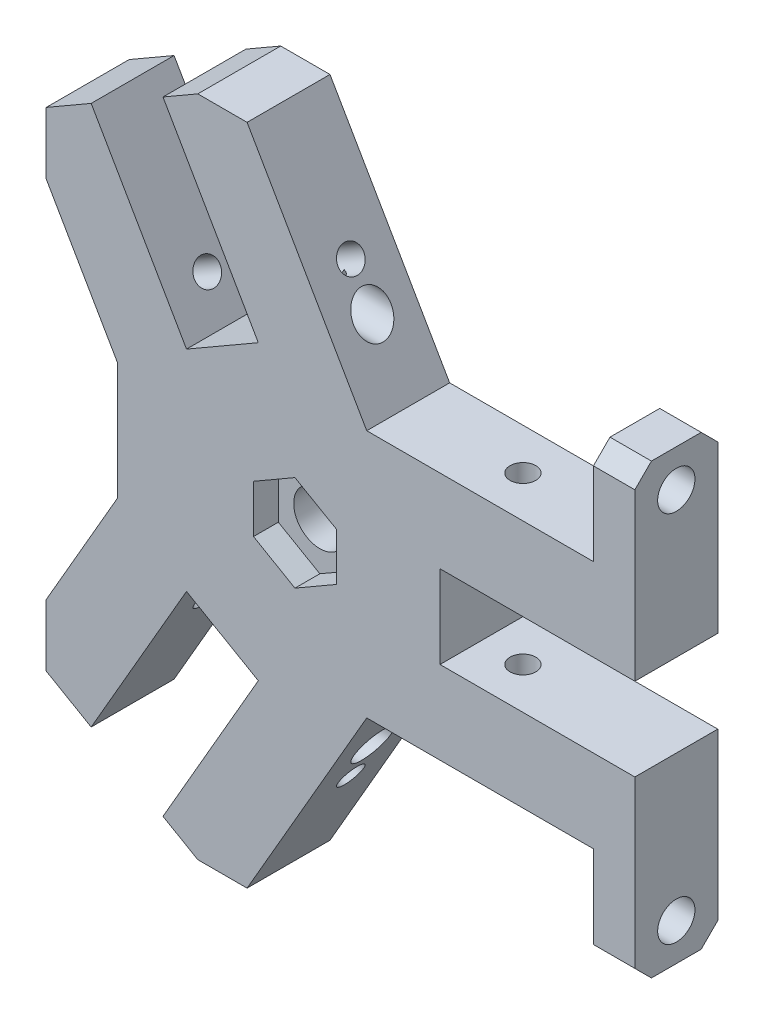
SolidWorks part; units mm, degrees
ref_plane "Front" through (0, 0, 0) normal (0, 0, 1) x (1, 0, 0)
ref_plane "Top" through (0, 0, 0) normal (0, 1, 0) x (1, 0, 0)
ref_plane "Right" through (0, 0, 0) normal (1, 0, 0) x (0, 0, -1)
sketch "Sketch1" plane through (0, 0, 0) normal (0, 0, 1) x (1, 0, 0)
  line L1 (0, 0) -> (71, 0)
  line L2 (0, 0) -> (0, 80)
  line L3 (0, 80) -> (71, 80)
  line L4 (71, 0) -> (71, 80)
  dimension "D1" = 80
  dimension "D2" = 71
extrude "Boss-Extrude1" add sketch "Sketch1" along normal blind 10
sketch "Sketch2" plane through (0, 0, 10) normal (0, 0, 1) x (1, 0, 0)
  line L1 (0, 80) -> (0, 0) construction
  line L2 (18.75, 59.4856) -> (18.75, 20.5144) construction
  line L3 (18.75, 20.5144) -> (52.5, 40) construction
  line L4 (52.5, 40) -> (18.75, 59.4856) construction
  circle A0 centre (30, 40) radius 22.5 construction
  point P3 (0, 40)
  dimension "D1" = 22.5
  dimension "D3" = 30
ref_axis "Axis1" through (30, 40, 10) along (0, 0, -1)
sketch "Sketch3" plane through (0, 0, 10) normal (0, 0, 1) x (1, 0, 0)
  line L0 (25.5801, 57.6554) -> (16.9199, 52.6554)
  line L1 (25.5801, 57.6554) -> (20.5801, 66.3157)
  line L2 (16.9199, 52.6554) -> (11.9199, 61.3157)
  line L3 (20.5801, 66.3157) -> (11.9199, 61.3157)
  line L4 (25.5801, 57.6554) -> (11.9199, 61.3157) construction
  line L5 (16.9199, 52.6554) -> (20.5801, 66.3157) construction
  line L6 (11.9199, 18.6843) -> (20.5801, 13.6843)
  line L7 (11.9199, 18.6843) -> (16.9199, 27.3446)
  line L8 (20.5801, 13.6843) -> (25.5801, 22.3446)
  line L9 (16.9199, 27.3446) -> (25.5801, 22.3446)
  line L10 (11.9199, 18.6843) -> (25.5801, 22.3446) construction
  line L11 (20.5801, 13.6843) -> (16.9199, 27.3446) construction
  line L13 (47.5, 45) -> (57.5, 45)
  line L14 (47.5, 45) -> (47.5, 35)
  line L15 (47.5, 35) -> (57.5, 35)
  line L16 (57.5, 45) -> (57.5, 35)
  line L17 (47.5, 45) -> (57.5, 35) construction
  line L18 (47.5, 35) -> (57.5, 45) construction
  point P0 (52.5, 40)
  point P1 (18.75, 59.4856)
  point P2 (18.75, 20.5144)
  dimension "D1" = 60
  dimension "D2" = 60
  dimension "D3" = 10
  dimension "D4" = 10
  dimension "D5" = 10
  dimension "D6" = 10
  dimension "D7" = 10
  dimension "D8" = 10
extrude "Cut-Extrude1" cut sketch "Sketch3" against normal blind 10
sketch "Sketch4" plane through (0, 45, 0) normal (0, -1, 0) x (1, 0, 0)
  line L0 (52.5, 7.2) -> (71, 7.2)
  line L1 (71, 10) -> (71, 0) construction
  line L2 (71, 7.2) -> (71, 2.8)
  line L3 (71, 2.8) -> (52.5, 2.8)
  line L4 (57.5, 10) -> (47.5, 10) construction
  arc A0 (52.5, 2.8) -> (52.5, 7.2) centre (52.5, 5) cw
  point P10 (52.5, 10)
  dimension "D1" = 2.2
  dimension "D2" = 5
sketch "Sketch5" plane through (0, 0, 10) normal (0, 0, 1) x (1, 0, 0)
  line L1 (57.5, 45) -> (85.6587, 45)
  line L2 (57.5, 45) -> (57.5, 35)
  line L3 (57.5, 35) -> (85.6587, 35)
  line L4 (85.6587, 45) -> (85.6587, 35)
extrude "Cut-Extrude3" cut sketch "Sketch5" against normal blind 10
sketch "Sketch6" plane through (9.5096, -5.4904, 0) normal (-0.866, 0.5, 0) x (0, 0, 1)
  line L0 (2.8, 27.141) -> (2.8, -15.6837)
  line L1 (2.8, -15.6837) -> (7.2, -15.6837)
  line L2 (7.2, -15.6837) -> (7.2, 27.141)
  line L3 (10, 22.141) -> (10, 32.141) construction
  arc A0 (2.8, 27.141) -> (7.2, 27.141) centre (5, 27.141) cw
  point P8 (10, 27.141)
  dimension "D1" = 2.2
  dimension "D2" = 5
  dimension "D3" = 4.4
pattern_circular "CirPattern1" count 3 over 360 about axis through (30, 40, 10) along (0, 0, -1) of "Cut-Extrude3"
ref_plane "Plane1" through (39.8205, 22.9904, 0) normal (0.866, 0.5, 0) x (0, 0, -1)
ref_plane "Plane2" through (5.1795, -2.9904, 0) normal (-0.866, 0.5, 0) x (0, 0, -1)
sketch "Sketch7" plane through (44.1506, 25.4904, 0) normal (-0.866, -0.5, 0) x (0, 0, 1)
  line L0 (2.8, 42.141) -> (2.8, 92.141)
  line L1 (2.8, 92.141) -> (7.2, 92.141)
  line L2 (7.2, 92.141) -> (7.2, 42.141)
  line L3 (10, 37.141) -> (10, 62.9423) construction
  arc A0 (2.8, 42.141) -> (7.2, 42.141) centre (5, 42.141) ccw
  dimension "D1" = 2.2
  dimension "D2" = 5
  dimension "D3" = 4.4
  dimension "D4" = 50
hole_wizard "M6 Clearance Hole1" positions "Sketch8" profile "Sketch9" hole size "M6" standard "ISO" end condition through all
sketch "Sketch8" plane through (0, 0, 10) normal (0, 0, 1) x (1, 0, 0)
  point P0 (30, 40)
sketch "Sketch9" plane through (30, 40, 10) normal (1, 0, 0) x (0, -1, 0)
  line L0 (0, 0) -> (0, 10)
  line L1 (0, 10) -> (3.15, 10)
  line L2 (3.15, 10) -> (3.15, 0)
  line L5 (3.15, 0) -> (0, 0)
  line L11 (0, -6.35) -> (0, 107.95) construction
  dimension "Thru Hole Dia." = 6.3
  dimension "Thru Hole Depth" = 10
sketch "Sketch10" plane through (0, 0, 10) normal (0, 0, 1) x (1, 0, 0)
  line L0 (16.9199, 52.6554) -> (25.5801, 57.6554) construction
  line L1 (30, 45.7735) -> (25, 42.8868)
  line L2 (25, 42.8868) -> (25, 37.1132)
  line L3 (25, 37.1132) -> (30, 34.2265)
  line L4 (30, 34.2265) -> (35, 37.1132)
  line L5 (35, 37.1132) -> (35, 42.8868)
  line L6 (35, 42.8868) -> (30, 45.7735)
  circle A0 centre (30, 40) radius 5 construction
  dimension "D1" = 10
extrude "Cut-Extrude6" cut sketch "Sketch10" against normal blind 3
ref_axis "Axis2" through (30, 40, 0) along (0, 0, 1)
ref_plane "Plane4" through (30, 0, 0) normal (-1, 0, 0) x (0, 0, 1)
sketch "Sketch11" plane through (0, 0, 0) normal (0, -1, 0) x (1, 0, 0)
  line L0 (12.6795, 10) -> (71, 10) construction
  line L3 (30, 1.65) -> (30, -1.65) construction
  circle A0 centre (52.5, 5) radius 1.55
  dimension "D1" = 3.1
  dimension "D2" = 5
  dimension "D3" = 22.5
extrude "Cut-Extrude7" cut sketch "Sketch11" against normal through all
pattern_circular "CirPattern2" count 3 over 360 about axis through (30, 40, 7) along (0, 0, -1) of "Cut-Extrude7"
sketch "Sketch12" plane through (0, 0, 10) normal (0, 0, 1) x (1, 0, 0)
  line L0 (71, 0) -> (71, 25)
  line L1 (71, 0) -> (71, 35) construction
  line L2 (71, 25) -> (38.6603, 25)
  line L3 (38.6603, 25) -> (24.2265, 0)
  line L4 (12.6795, 0) -> (71, 0) construction
  line L5 (24.2265, 0) -> (71, 0)
  line L6 (12.6795, 0) -> (25.5801, 22.3446) construction
  line L8 (47.5, 35) -> (71, 35) construction
  dimension "D1" = 10
  dimension "D2" = 10
extrude "Cut-Extrude8" cut sketch "Sketch12" against normal blind 10
ref_plane "Plane3" through (0, 40, 0) normal (0, -1, 0) x (-1, 0, 0)
mirror "Mirror1" about plane through (0, 40, 0) normal (0, -1, 0) of "Cut-Extrude8"
sketch "Sketch13" plane through (0, 0, 10) normal (0, 0, 1) x (1, 0, 0)
  line L0 (0, 61.9615) -> (8.6244, 47.0237)
  line L1 (0, 80) -> (0, 0) construction
  line L2 (8.6244, 47.0237) -> (8.6244, 32.9763)
  line L3 (8.6244, 32.9763) -> (0, 18.0385)
  line L4 (0, 18.0385) -> (0, 61.9615)
  line L5 (1.1325, 80) -> (16.9199, 52.6554) construction
  line L6 (16.9199, 27.3446) -> (1.1325, 0) construction
  circle A0 centre (30, 40) radius 22.5 construction
  dimension "D1" = 10
extrude "Cut-Extrude9" cut sketch "Sketch13" against normal blind 10
sketch "Sketch14" plane through (0, 0, 10) normal (0, 0, 1) x (1, 0, 0)
  line L0 (-3.2404, 12.426) -> (22.7404, -2.574)
  line L1 (22.7404, -2.574) -> (18.1699, -10.4904)
  line L2 (18.1699, -10.4904) -> (-7.8109, 4.5096)
  line L3 (-7.8109, 4.5096) -> (-3.2404, 12.426)
  line L4 (25.5801, 22.3446) -> (16.9199, 27.3446) construction
  line L5 (38.6603, 25) -> (24.2265, 0) construction
  line L6 (0, 18.0385) -> (8.6244, 32.9763) construction
  dimension "D1" = 23
extrude "Cut-Extrude10" cut sketch "Sketch14" against normal blind 10
mirror "Mirror2" about plane through (0, 40, 0) normal (0, -1, 0) of "Cut-Extrude10"
sketch "Sketch15" plane through (0, 0, 10) normal (0, 0, 1) x (1, 0, 0)
  line L0 (71, 45) -> (71, 55) construction
  line L1 (71, 19) -> (182, 19)
  line L2 (71, 19) -> (71, 61)
  line L3 (71, 61) -> (182, 61)
  line L4 (182, 19) -> (182, 61)
  line L5 (0, 0) -> (0, 81.4596) construction
  point P6 (71, 40)
  dimension "D1" = 42
  dimension "D2" = 182
extrude "Boss-Extrude2" add sketch "Sketch15" against normal blind 10
sketch "Sketch16" plane through (0, 0, 10) normal (0, 0, 1) x (1, 0, 0)
  line L1 (71, 50.5) -> (96, 50.5)
  line L2 (71, 50.5) -> (71, 29.5)
  line L3 (71, 29.5) -> (96, 29.5)
  line L4 (96, 50.5) -> (96, 29.5)
  line L5 (71, 45) -> (71, 35) construction
  line L7 (182, 61) -> (71, 61) construction
  dimension "D1" = 25
  dimension "D2" = 21
  dimension "D3" = 10.5
sketch "Sketch18" plane through (0, 0, 10) normal (0, 0, 1) x (1, 0, 0)
  line L0 (182, 61) -> (71, 61) construction
  line L1 (113.8, 24.5) -> (82.8, 24.5)
  line L2 (113.8, 24.5) -> (113.8, 55.5)
  line L3 (113.8, 55.5) -> (82.8, 55.5)
  line L4 (82.8, 24.5) -> (82.8, 55.5)
  line L5 (113.8, 24.5) -> (82.8, 55.5) construction
  line L6 (113.8, 55.5) -> (82.8, 24.5) construction
  line L7 (71, 61) -> (71, 55) construction
  point P0 (98.3, 40)
  dimension "D1" = 31
  dimension "D2" = 31
  dimension "D3" = 68.3
  dimension "D4" = 5.5
  dimension "D5" = 11.8
sketch "Sketch21" plane through (0, 0, 10) normal (0, 0, 1) x (1, 0, 0)
  line L4 (97.55, 40) -> (99.05, 40) construction
  line L5 (113.8, 24.5) -> (82.8, 55.5) construction
  line L6 (97.55, 47.5) -> (99.05, 47.5)
  line L7 (97.55, 32.5) -> (99.05, 32.5)
  arc A2 (97.55, 47.5) -> (97.55, 32.5) centre (97.55, 40) ccw
  arc A3 (99.05, 32.5) -> (99.05, 47.5) centre (99.05, 40) ccw
  point P5 (98.3, 40)
  dimension "D1" = 15
  dimension "D2" = 1.5
sketch "Sketch22" plane through (0, 0, 10) normal (0, 0, 1) x (1, 0, 0)
  line L0 (182, 19) -> (182, 61) construction
  line L1 (182, 67) -> (167, 67)
  line L2 (182, 67) -> (182, 13)
  line L3 (182, 13) -> (167, 13)
  line L4 (167, 67) -> (167, 13)
  point P6 (182, 40)
  dimension "D1" = 15
  dimension "D2" = 54
extrude "Boss-Extrude3" add sketch "Sketch22" against normal blind 10
sketch "Sketch23" plane through (182, 0, 0) normal (1, 0, 0) x (0, 0, -1)
  line L0 (-5, 62.5) -> (-5, 17.5) construction
  point P2 (-5, 40)
  dimension "D1" = 45
  dimension "D2" = 5
hole_wizard "M4 Clearance Hole1" positions "Sketch24" profile "Sketch25" hole size "M4" standard "DIN"
sketch "Sketch24" plane through (182, 0, 0) normal (1, 0, 0) x (0, 0, -1)
  point P0 (-5, 62.5)
  point P3 (-5, 17.5)
sketch "Sketch25" plane through (182, 62.5, 5) normal (0, 1, 0) x (0, 0, -1)
  line L0 (0, 0) -> (0, 31.3519)
  line L1 (0, 31.3519) -> (2.25, 30)
  line L2 (2.25, 30) -> (2.25, 0)
  line L5 (2.25, 0) -> (0, 0)
  line L10 (0, 31.3519) -> (-2.25, 30) construction
  line L11 (0, -6.35) -> (0, 107.95) construction
  dimension "Hole Dia." = 4.5
  dimension "Hole Depth" = 30
  dimension "Drill Angle" = 118
sketch "Sketch26" plane through (0, 0, 10) normal (0, 0, 1) x (1, 0, 0)
  line L0 (119.3, 61) -> (119.3, 55)
  line L1 (167, 61) -> (71, 61) construction
  line L2 (119.3, 55) -> (167, 55)
  line L3 (167, 55) -> (167, 61)
  line L4 (167, 61) -> (119.3, 61)
  dimension "D1" = 5.5
  dimension "D2" = 6
extrude "Cut-Extrude13" cut sketch "Sketch26" against normal blind 10
mirror "Mirror3" about plane through (0, 40, 0) normal (0, -1, 0) of "Cut-Extrude13"
chamfer "Chamfer1" distance 4 angle 60 2 edges at (119.3, 25, 5) (119.3, 55, 5) first distance on face at (143.15, 25, 5) first distance on face at (143.15, 55, 5)
sketch "Sketch27" plane through (0, 0, 10) normal (0, 0, 1) x (1, 0, 0)
  line L1 (71, 61) -> (77.3, 61)
  line L2 (71, 61) -> (71, 55)
  line L3 (71, 55) -> (77.3, 55)
  line L4 (77.3, 61) -> (77.3, 55)
  dimension "D1" = 6
  dimension "D2" = 5.5
extrude "Cut-Extrude14" cut sketch "Sketch27" against normal blind 10
mirror "Mirror4" about plane through (0, 40, 0) normal (0, -1, 0) of "Cut-Extrude14"
chamfer "Chamfer2" distance 4 angle 60 2 edges at (77.3, 55, 5) (77.3, 25, 5) first distance on face at (57.9801, 55, 5) first distance on face at (57.9801, 25, 5)
extrude "Cut-Extrude15" cut sketch "Sketch21" against normal blind 10
sketch "Sketch28" plane through (0, 0, 10) normal (0, 0, 1) x (1, 0, 0)
  line L0 (97.55, 40) -> (99.05, 40) construction
  line L1 (97.55, 51.25) -> (99.05, 51.25)
  line L2 (97.55, 28.75) -> (99.05, 28.75)
  circle A0 centre (98.3, 40) radius 11 construction
  arc A1 (97.55, 51.25) -> (97.55, 28.75) centre (97.55, 40) ccw
  arc A2 (99.05, 28.75) -> (99.05, 51.25) centre (99.05, 40) ccw
  point P5 (98.3, 40)
  dimension "D1" = 22
  dimension "D2" = 11.25
  dimension "D3" = 1.5
extrude "Cut-Extrude16" cut sketch "Sketch28" against normal blind 2.2
sketch "Sketch29" plane through (0, 0, 10) normal (0, 0, 1) x (1, 0, 0)
  line L0 (82.05, 55.5) -> (83.55, 55.5) construction
  line L1 (113.8, 55.5) -> (82.8, 55.5) construction
  line L2 (82.05, 57.2) -> (83.55, 57.2)
  line L3 (82.05, 53.8) -> (83.55, 53.8)
  line L4 (113.05, 53.8) -> (114.55, 53.8)
  line L5 (113.05, 57.2) -> (114.55, 57.2)
  line L6 (113.05, 55.5) -> (114.55, 55.5) construction
  line L7 (113.05, 22.8) -> (114.55, 22.8)
  line L8 (113.05, 26.2) -> (114.55, 26.2)
  line L9 (113.05, 24.5) -> (114.55, 24.5) construction
  line L10 (82.05, 22.8) -> (83.55, 22.8)
  line L11 (82.05, 26.2) -> (83.55, 26.2)
  line L12 (82.05, 24.5) -> (83.55, 24.5) construction
  arc A0 (82.05, 57.2) -> (82.05, 53.8) centre (82.05, 55.5) ccw
  arc A1 (83.55, 53.8) -> (83.55, 57.2) centre (83.55, 55.5) ccw
  arc A2 (113.05, 57.2) -> (113.05, 53.8) centre (113.05, 55.5) ccw
  arc A3 (114.55, 53.8) -> (114.55, 57.2) centre (114.55, 55.5) ccw
  arc A4 (113.05, 26.2) -> (113.05, 22.8) centre (113.05, 24.5) ccw
  arc A5 (114.55, 22.8) -> (114.55, 26.2) centre (114.55, 24.5) ccw
  arc A6 (82.05, 26.2) -> (82.05, 22.8) centre (82.05, 24.5) ccw
  arc A7 (83.55, 22.8) -> (83.55, 26.2) centre (83.55, 24.5) ccw
  point P5 (82.8, 55.5)
  point P15 (113.8, 55.5)
  point P22 (113.8, 24.5)
  point P29 (82.8, 24.5)
  dimension "D1" = 3.4
  dimension "D2" = 1.5
  dimension "D3" = 2
  dimension "D4" = 2
extrude "Cut-Extrude17" cut sketch "Sketch29" against normal blind 10
sketch "Sketch30" plane through (0, 0, 10) normal (0, 0, 1) x (1, 0, 0)
  line L0 (167, 67) -> (167, 55) construction
  line L1 (134, 29.5) -> (155, 29.5) construction
  line L2 (134, 29.5) -> (134, 50.5) construction
  line L3 (134, 50.5) -> (155, 50.5) construction
  line L4 (155, 29.5) -> (155, 50.5) construction
  line L6 (123.3, 55) -> (167, 55) construction
  dimension "D1" = 21
  dimension "D2" = 21
  dimension "D3" = 12
  dimension "D4" = 4.5
hole_wizard "M4 Clearance Hole2" positions "Sketch31" profile "Sketch32" hole size "M4" standard "DIN" end condition through all
sketch "Sketch31" plane through (0, 0, 10) normal (0, 0, 1) x (1, 0, 0)
  point P0 (134, 50.5)
  point P3 (155, 50.5)
  point P6 (155, 29.5)
  point P9 (134, 29.5)
sketch "Sketch32" plane through (134, 50.5, 10) normal (1, 0, 0) x (0, -1, 0)
  line L0 (0, 0) -> (0, 10)
  line L1 (0, 10) -> (2.25, 10)
  line L2 (2.25, 10) -> (2.25, 0)
  line L5 (2.25, 0) -> (0, 0)
  line L11 (0, -6.35) -> (0, 107.95) construction
  dimension "Thru Hole Dia." = 4.5
  dimension "Thru Hole Depth" = 10
sketch "Sketch33" plane through (71, 0, 0) normal (-1, 0, 0) x (0, 0, 1)
  line L1 (-10, 85) -> (20, 85)
  line L2 (-10, 85) -> (-10, -5)
  line L3 (-10, -5) -> (20, -5)
  line L4 (20, 85) -> (20, -5)
  dimension "D1" = 10
  dimension "D2" = 30
  dimension "D3" = 90
  dimension "D4" = 5
extrude "Cut-Extrude18" cut sketch "Sketch33" against normal through all contours L4 L3 L2 L1
sketch "Sketch34" plane through (71, 0, 0) normal (1, 0, 0) x (0, 0, -1)
  line L5 (0, 45) -> (0, 67)
  line L6 (0, 67) -> (-10, 67)
  line L7 (-10, 67) -> (-10, 45)
  line L8 (0, 45) -> (0, 35) construction
  line L9 (-10, 45) -> (0, 45)
  point P18 (0, 40)
  dimension "D1" = 27
  dimension "D2" = 22
  dimension "D3" = 10
  dimension "D4" = 10
extrude "Boss-Extrude4" add sketch "Sketch34" against normal blind 5
mirror "Mirror5" about plane through (0, 40, 0) normal (0, -1, 0) of "Boss-Extrude4"
sketch "Sketch35" plane through (71, 0, 0) normal (1, 0, 0) x (0, 0, -1)
  line L0 (-5, 62.5) -> (-5, 17.5)
  line L1 (-10, 67) -> (-10, 45) construction
  line L2 (0, 67) -> (-10, 67) construction
  dimension "D1" = 45
  dimension "D2" = 5
  dimension "D3" = 4.5
sketch "Sketch38" plane through (71, 0, 0) normal (1, 0, 0) x (0, 0, -1)
  circle A0 centre (-5, 62.5) radius 2.25
  circle A1 centre (-5, 17.5) radius 2.25
  dimension "D1" = 4.5
  dimension "D2" = 4.5
extrude "Cut-Extrude20" cut sketch "Sketch38" against normal blind 41
chamfer "Chamfer3" distance 2 angle 45 4 edges at (68.5, 67, 0) (68.5, 67, 10) (68.5, 13, 0) (68.5, 13, 10)
